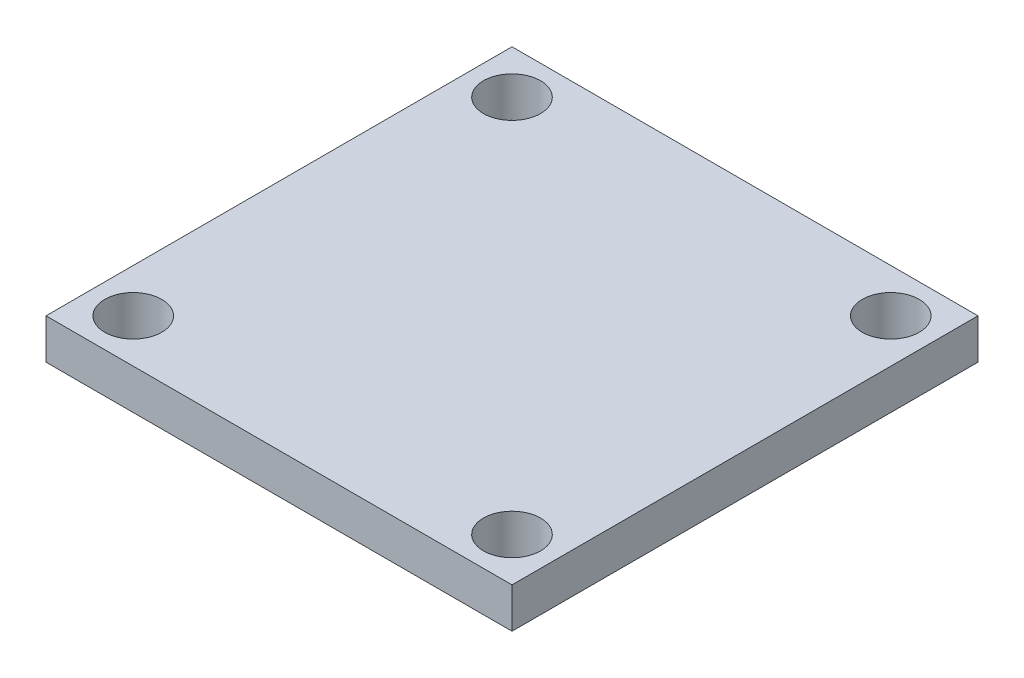
SolidWorks part; units mm, degrees
ref_plane "Front Plane" through (0, 0, 0) normal (0, 0, 1) x (1, 0, 0)
ref_plane "Top Plane" through (0, 0, 0) normal (0, 1, 0) x (1, 0, 0)
ref_plane "Right Plane" through (0, 0, 0) normal (1, 0, 0) x (0, 0, -1)
sketch "Sketch1" plane through (0, 0, 0) normal (0, 1, 0) x (1, 0, 0)
  line L0 (-23.57, 0) -> (23.57, 0) construction
  line L1 (-29, -29) -> (29, -29)
  line L2 (-29, -29) -> (-29, 29)
  line L3 (-29, 29) -> (29, 29)
  line L4 (29, -29) -> (29, 29)
  line L5 (-29, -29) -> (29, 29) construction
  line L6 (-29, 29) -> (29, -29) construction
  line L7 (-23.57, -29) -> (-23.57, -23.57) construction
  line L8 (-23.57, -23.57) -> (-29, -23.57) construction
  line L9 (0, -29) -> (0, 29) construction
  circle A0 centre (-23.57, -23.57) radius 2.55 construction
  circle A1 centre (23.57, -23.57) radius 2.55 construction
  circle A2 centre (23.57, 23.57) radius 2.55 construction
  circle A3 centre (-23.57, 23.57) radius 2.55 construction
  circle A4 centre (-23.57, 23.57) radius 3.55
  circle A5 centre (23.57, 23.57) radius 3.55
  circle A6 centre (23.57, -23.57) radius 3.55
  circle A7 centre (-23.57, -23.57) radius 3.55
  point P0 (0, 0)
  point P9 (0, 0)
  dimension "D3" = 5.1
  dimension "D4" = 7.1
  dimension "D1" = 58
  dimension "D2" = 47.14
extrude "Boss-Extrude1" add sketch "Sketch1" along normal blind 5
